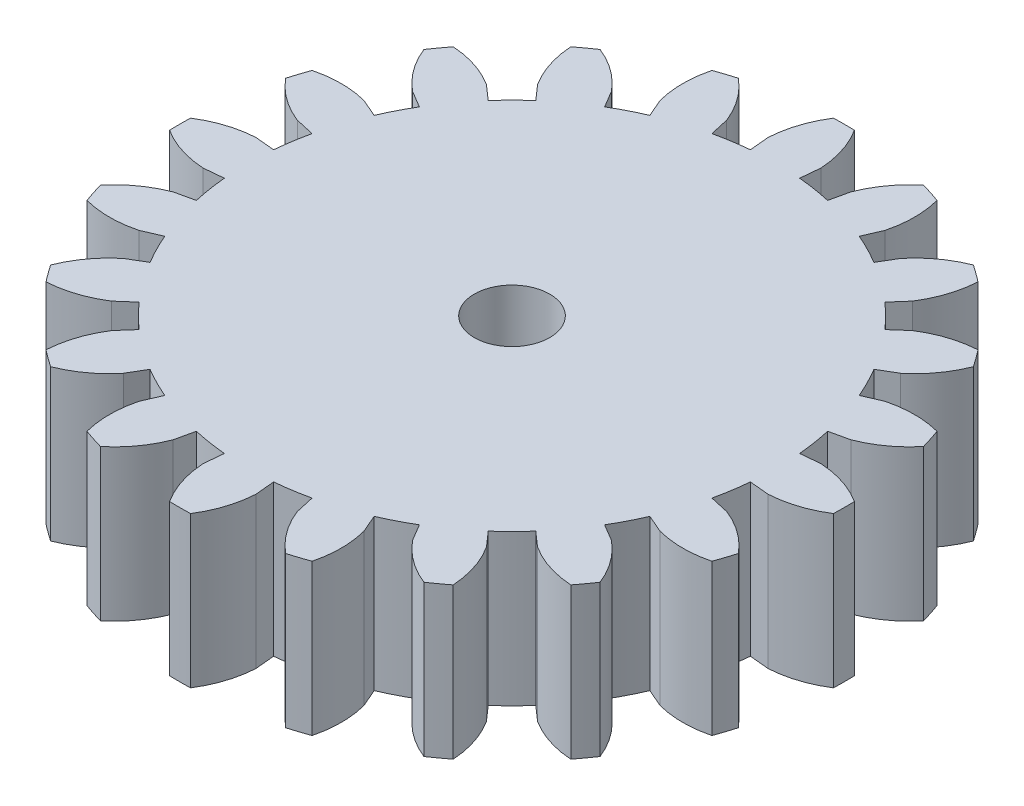
SolidWorks part; units mm, degrees
ref_plane "Спереди" through (0, 0, 0) normal (0, 0, 1) x (1, 0, 0)
ref_plane "Сверху" through (0, 0, 0) normal (0, 1, 0) x (1, 0, 0)
ref_plane "Справа" through (0, 0, 0) normal (1, 0, 0) x (0, 0, -1)
other "Configuration Table"
sketch "Эскиз1" plane through (0, 0, 0) normal (0, 1, 0) x (1, 0, 0)
  circle A0 centre (0, 0) radius 17.5
  dimension "D1" = 35
extrude "Бобышка-Вытянуть1" add sketch "Эскиз1" along normal blind 10
sketch "Эскиз2" plane through (0, 0, 0) normal (0, -1, 0) x (1, 0, 0)
  line L0 (0, 0) -> (0, 22) construction
  line L1 (0, 0) -> (-1.7523, 18.712) construction
  line L2 (0, 0) -> (1.7523, 18.712) construction
  line L5 (-1.5692, 19.9383) -> (0, 0) construction
  line L6 (0, 0) -> (1.5692, 19.9383) construction
  line L7 (-0.6949, 21.989) -> (0, 0) construction
  line L8 (-1.6317, 17.4238) -> (-1.7523, 18.712)
  line L9 (1.7523, 18.712) -> (1.6317, 17.4238)
  circle A0 centre (0, 0) radius 18.7938 construction
  circle A1 centre (0, 0) radius 20 construction
  circle A2 centre (0, 0) radius 22 construction
  arc A3 (-0.6949, 21.989) -> (0.6949, 21.989) centre (0, 0) cw
  arc A4 (-1.6317, 17.4238) -> (1.6317, 17.4238) centre (0, 0) cw
  circle A5 centre (0, 0) radius 17.5 construction
  arc A6 (-1.5692, 19.9383) -> (1.5692, 19.9383) centre (0, 0) cw construction
  arc A7 (-1.7523, 18.712) -> (-0.6949, 21.989) centre (5.0681, 18.3203) cw
  arc A8 (0.6949, 21.989) -> (1.7523, 18.712) centre (-5.0681, 18.3203) cw
  point P12 (0, 20)
  point P16 (0, 22)
  point P22 (0, 17.5)
  dimension "D1" = 37.5877
  dimension "D2" = 40
  dimension "D3" = 44
  dimension "D4" = 5.35
  dimension "D5" = 4.5
  dimension "D6" = 1.81
extrude "Бобышка-Вытянуть2" add sketch "Эскиз2" against normal blind 10
pattern_circular "Круговой массив1" count 20 over 360 about axis through (0, 10, 0) along (0, -1, 0) of "Бобышка-Вытянуть2" reverse direction yes
sketch "Эскиз3" plane through (0, 0, 0) normal (0, -1, 0) x (1, 0, 0)
  circle A0 centre (0, 0) radius 2.5
  dimension "D1" = 5
extrude "Вырез-Вытянуть1" cut sketch "Эскиз3" against normal through all
equation "\"Ширина груза\"= 420"
equation "\"Глубина груза\"= 490"
equation "\"Высота груза\"= 297"
equation "\"Ширина ячейки\"= \"Ширина груза\" + 10"
equation "\"Глубина ячейки\"= \"Глубина груза\" + 10"
equation "\"Высота ячейки\"= \"Высота груза\" + 10 + 13"
equation "\"Колво ячеек ширина\"= 2"
equation "\"Колво ячеек высота\"= 2"
equation "\"Толщина стенки\" = 6"
equation "\"Крепление дверцы\"= 5"
equation "\"Ширина рейки\"= \"Толщина шестерни\""
equation "\"Высота рейки\"= 20"
equation "\"Высота пола\"= 20"
equation "\"Колво полозьев\"= 5"
equation "\"Отступ рейки\"= 20"
equation "\"Глубина каретки\"= \"Глубина ячейки\" + 30 + \"Мотор Y высота корпуса\" + 20"
equation "\"Длинна рейки\"= ( \"Ширина ячейки\" + \"Толщина стенки\" + \"Крепление дверцы\" ) * \"Колво ячеек ширина\" + \"Ширина ячейки выгрузки\" * \"Колво выгрузки\" + \"Толщина стенки\""
equation "\"Отступ шпильки\"= 26"
equation "\"Диаметр шпильки\"= 5"
equation "\"Длинна шпильки\"= ( \"Высота ячейки\" + \"Толщина стенки\" + \"Высота пола\" ) * \"Колво ячеек высота\" + ( \"Толщина стенки\" + \"Отступ рейки\" ) * 2 "
equation "\"Ширина пластины\"= 50  "
equation "\"Высота зона выгрузки\"= \"Высота ячейки\" * 2 + \"Толщина стенки\" * 2"
equation "\"Колво выгрузки\"= 1"
equation "\"Ширина ячейки выгрузки\"= \"Ширина ячейки\" + \"Толщина стенки\" + \"Отступ крепления мотора фиксации\"*2"
equation "\"Отступ крепления мотора фиксации\" = 30"
equation "\"Мотор X ширина корпуса\"= 42.3"
equation "\"Мотор X высота корпуса\"= 42.3"
equation "\"Мотор X длина корпуса\"= 40"
equation "\"Мотор X вылет вала\"= 19.8"
equation "\"Мотор Y ширина корпуса\"= 42.3"
equation "\"Мотор Y высота корпуса\"= 42.3"
equation "\"Мотор Y длина корпуса\"= 48"
equation "\"Мотор Y вылет вала\"= 30"
equation "\"Мотор Z ширина корпуса\"= 42"
equation "\"Мотор Z высота корпуса\"= 42"
equation "\"Мотор Z длина корпуса\"= 40"
equation "\"Мотор Z вылет вала\"= 23"
equation "\"Мотор диаметр вала ПРЕДВ\"= 5"
equation "\"Мотор шаг крепления ПРЕДВ\"= 31"
equation "\"Мотор диаметр отверстий ПРЕДВ\"= 3"
equation "\"Мотор глубина отверстий ПРЕДВ\"= 4.5"
equation "\"Мотор диаметр буртика ПРЕДВ\"= 22"
equation "\"Мотор высота буртика ПРЕДВ\"= 2"
equation "\"Мотор диаметр шкива ПРЕДВ\"= 16"
equation "\"Мотор длина шкива ПРЕДВ\"= 12"
equation "\"Мотор отступ шкива ПРЕДВ\"= 5"
equation "\"Мотор X шаг градусов\"= 1.8"
equation "\"Мотор Y шаг градусов\"= 1.8"
equation "\"Мотор Z шаг градусов\"= 1.8"
equation "\"Мотор Y диаметр ротора\"= 25.78"
equation "\"Толщина шестерни\"= 10"
equation "\"D1@Бобышка-Вытянуть1\"=\"Толщина шестерни\""
equation "\"D1@Бобышка-Вытянуть2\"=\"Толщина шестерни\""
equation "\"D1@Эскиз3\"=\"Мотор диаметр вала ПРЕДВ\""
